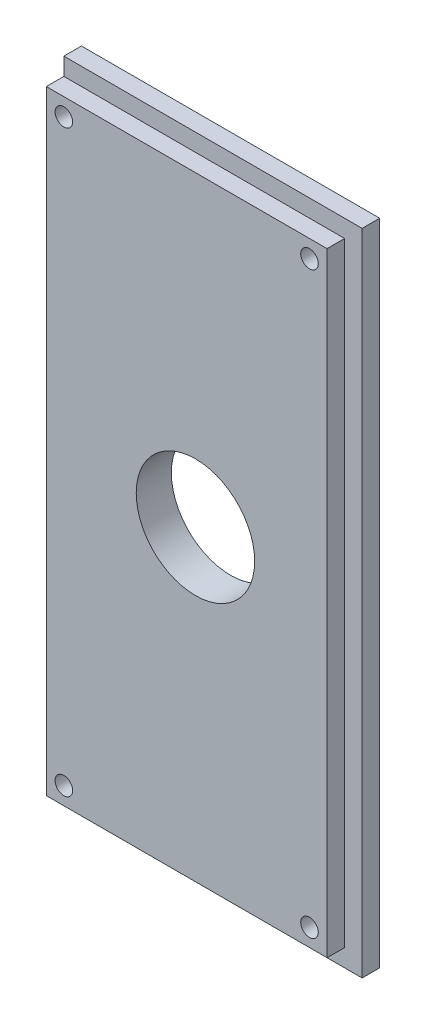
SolidWorks part; units mm, degrees
ref_plane "Plan de face" through (0, 0, 0) normal (0, 0, 1) x (1, 0, 0)
ref_plane "Plan de dessus" through (0, 0, 0) normal (0, 1, 0) x (1, 0, 0)
ref_plane "Plan de droite" through (0, 0, 0) normal (1, 0, 0) x (0, 0, -1)
sketch "Esquisse1" plane through (0, 0, 0) normal (0, 0, 1) x (1, 0, 0)
  line L1 (-17, 37) -> (17, 37)
  line L2 (-17, 37) -> (-17, -37)
  line L3 (-17, -37) -> (17, -37)
  line L4 (17, 37) -> (17, -37)
  point P4 (0, 37)
  point P6 (-17, 0)
  dimension "D1" = 34
  dimension "D2" = 74
extrude "Boss.-Extru.1" add sketch "Esquisse1" along normal blind 2
sketch "Esquisse2" plane through (0, 0, 2) normal (0, 0, 1) x (1, 0, 0)
  line L0 (-17, 37) -> (-17, -37) construction
  line L1 (-17, 35) -> (15, 35)
  line L2 (-17, 35) -> (-17, -35)
  line L3 (-17, -35) -> (15, -35)
  line L4 (15, 35) -> (15, -35)
  line L5 (17, 37) -> (-17, 37) construction
  line L6 (17, -37) -> (17, 37) construction
  line L7 (-17, -37) -> (17, -37) construction
  dimension "D1" = 2
  dimension "D2" = 2
  dimension "D3" = 2
extrude "Boss.-Extru.2" add sketch "Esquisse2" along normal blind 2
sketch "Sketch1" plane through (0, 0, 0) normal (0, 0, -1) x (-1, 0, 0)
  circle A0 centre (0, 0) radius 6.75
  dimension "D1" = 13.5
extrude "Cut-Extrude1" cut sketch "Sketch1" against normal through all
sketch "Esquisse3" plane through (0, 0, 4) normal (0, 0, 1) x (1, 0, 0)
  line L0 (15, 35) -> (-17, 35) construction
  line L3 (-17, 35) -> (-17, -35) construction
  line L4 (15, -35) -> (15, 35) construction
  line L5 (-17, -35) -> (15, -35) construction
  circle A0 centre (-15, 33) radius 1
  circle A1 centre (13, 33) radius 1
  circle A2 centre (13, -33) radius 1
  circle A3 centre (-15, -33) radius 1
  point P12 (-17, 32.8592)
  point P13 (-17, 32.7778)
  point P14 (0, 0)
  point P15 (0, 0)
  point P16 (0, 0)
  point P17 (0, 0)
  point P18 (12.5107, 32.8)
  dimension "D1" = 2
  dimension "D2" = 2
  dimension "D3" = 2
  dimension "D4" = 2
  dimension "D5" = 2
extrude "Enlèv. mat.-Extru.1" cut sketch "Esquisse3" against normal through all
sketch "Esquisse4" plane through (0, 0, 0) normal (0, 0, -1) x (-1, 0, 0)
  line L0 (17, 37) -> (17, -37) construction
  line L1 (21, 5) -> (11, 5)
  line L2 (21, 5) -> (21, -5)
  line L3 (21, -5) -> (11, -5)
  line L4 (11, 5) -> (11, -5)
  point P4 (23.9005, -6.2954)
  point P5 (11, 0)
  dimension "D1" = 10
  dimension "D2" = 10
  dimension "D3" = 4
extrude "Boss.-Extru.3" add sketch "Esquisse4" along normal blind 2
fillet "Congé1" radius 2 5 edges at (-14, -5, 0) (-11, 0, 0) (-14, 5, 0) (-21, 5, -1) (-21, -5, -1)
